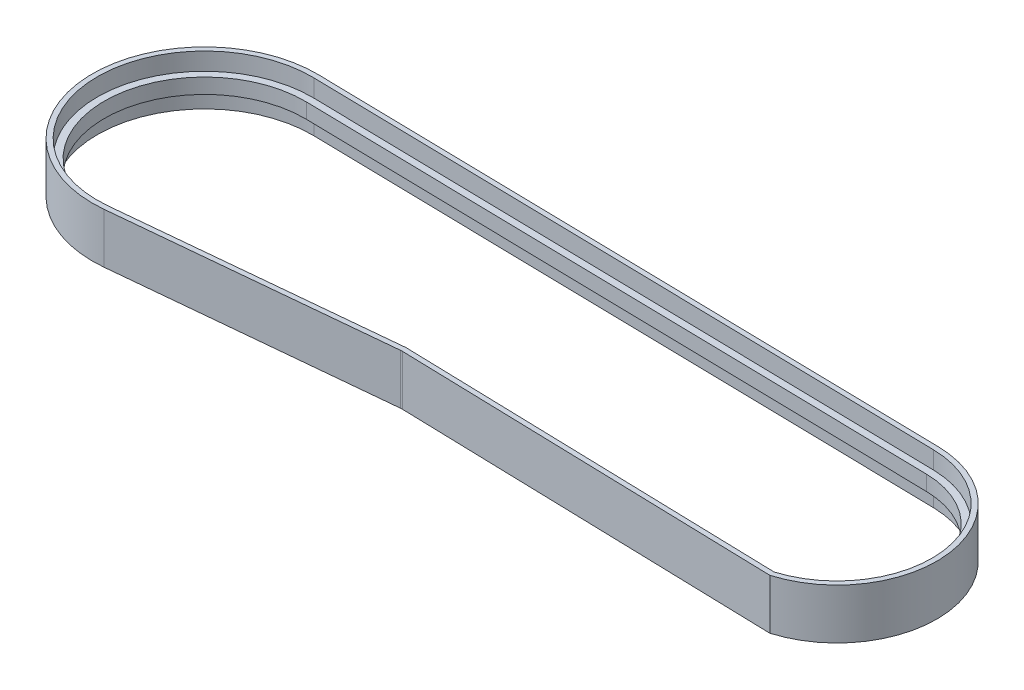
SolidWorks part; units mm, degrees
other "Markup1"
sketch "Sketch2" plane through (-23.4, 0, -23.4) normal (-0.231, -0.9167, -0.326) x (-0.972, 0.232, 0.0366)
sketch "Sketch3" plane through (-22.35, 0, -22.35) normal (-0.231, -0.9167, -0.326) x (-0.972, 0.232, 0.0366)
sketch "Sketch4" plane through (-22.35, 0, -22.35) normal (-0.231, -0.9167, -0.326) x (-0.972, 0.232, 0.0366)
sketch "Sketch5" plane through (-22.35, 0, -22.35) normal (-0.231, -0.9167, -0.326) x (-0.972, 0.232, 0.0366)
sketch "Sketch6" plane through (-22.35, 0, -22.35) normal (-0.231, -0.9167, -0.326) x (-0.972, 0.232, 0.0366)
material "BUTYL"
ref_plane "Front Plane" through (0, 0, 0) normal (0, 0, 1) x (1, 0, 0)
ref_plane "Top Plane" through (0, 0, 0) normal (0, 1, 0) x (1, 0, 0)
ref_plane "Right Plane" through (0, 0, 0) normal (1, 0, 0) x (0, 0, -1)
sketch "Sketch1" plane through (0, 0, 0) normal (0, 1, 0) x (1, 0, 0)
  line L0 (0, 0) -> (126, 0) construction
  line L1 (0.4151, 21.346) -> (126.3675, 18.8964)
  line L2 (0.4346, 22.3458) -> (126.3869, 19.8962)
  line L5 (8.122, -19.7447) -> (131.5335, -18.0718) construction
  line L6 (8.3239, -20.7421) -> (131.6879, -19.0698) construction
  line L7 (131.5335, -18.0718) -> (56.2608, -16.0228)
  line L8 (131.6879, -19.0698) -> (56.4768, -17.0225)
  line L9 (2.0539, -21.251) -> (55.9487, -16.0421)
  line L10 (2.1501, -22.2463) -> (56.0449, -17.0374)
  line L11 (0, 0) -> (56.3816, -20.5212) construction
  arc A0 (0.4151, 21.346) -> (2.0539, -21.251) centre (0, 0) ccw
  arc A1 (131.5335, -18.0718) -> (126.3675, 18.8964) centre (126, 0) ccw
  arc A2 (131.6879, -19.0698) -> (126.3869, 19.8962) centre (126, 0) ccw
  arc A3 (0.4346, 22.3458) -> (2.1501, -22.2463) centre (0, 0) ccw
  circle A4 centre (0, 0) radius 60 construction
  circle A5 centre (56.3816, -20.5212) radius 1.25 construction
  arc A6 (56.4768, -17.0225) -> (56.0449, -17.0374) centre (56.3816, -20.5212) ccw
  arc A8 (56.2608, -16.0228) -> (55.9487, -16.0421) centre (56.3816, -20.5212) ccw
  arc A9 (0.4346, 22.3458) -> (8.3239, -20.7421) centre (0, 0) ccw construction
  arc A10 (0.4151, 21.346) -> (8.122, -19.7447) centre (0, 0) ccw construction
  point P17 (45.2586, -17.6917)
  dimension "D1" = 42.7
  dimension "D3" = 37.8
  dimension "D5" = 120
  dimension "D6" = 7
  dimension "D7" = 2.5
  dimension "D9" = 1
  dimension "D2" = 126
  dimension "D8" = 20
  dimension "D4" = 1
extrude "Boss-Extrude1" add sketch "Sketch1" along normal mid plane 10
sketch "Sketch8" plane through (0, 0, 0) normal (0, 1, 0) x (1, 0, 0)
  line L15 (56.2636, -14.6224) -> (131.3381, -16.666)
  line L16 (126.3403, 17.4967) -> (0.3879, 19.9462)
  line L17 (1.9192, -19.8575) -> (55.814, -14.6486)
  line L18 (56.2636, -14.6224) -> (131.3381, -16.666)
  line L19 (126.3403, 17.4967) -> (0.3879, 19.9462)
  line L20 (1.9192, -19.8575) -> (55.814, -14.6486)
  line L32 (56.2608, -16.2229) -> (131.5607, -18.2726)
  line L33 (126.3714, 19.0964) -> (0.419, 21.5459)
  line L34 (2.0731, -21.45) -> (55.9679, -16.2412)
  line L35 (56.2608, -16.2229) -> (131.5607, -18.2726)
  line L36 (126.3714, 19.0964) -> (0.419, 21.5459)
  line L37 (2.0731, -21.45) -> (55.9679, -16.2412)
  arc A12 (56.2636, -14.6224) -> (55.814, -14.6486) centre (56.3816, -20.5212) ccw
  arc A13 (131.3381, -16.666) -> (126.3403, 17.4967) centre (126, 0) ccw
  arc A14 (0.3879, 19.9462) -> (1.9192, -19.8575) centre (0, 0) ccw
  arc A15 (56.2636, -14.6224) -> (55.814, -14.6486) centre (56.3816, -20.5212) ccw
  arc A16 (131.3381, -16.666) -> (126.3403, 17.4967) centre (126, 0) ccw
  arc A17 (0.3879, 19.9462) -> (1.9192, -19.8575) centre (0, 0) ccw
  arc A28 (56.2608, -16.2229) -> (55.9679, -16.2412) centre (56.3816, -20.5212) ccw
  arc A29 (131.5607, -18.2726) -> (126.3714, 19.0964) centre (126, 0) ccw
  arc A30 (0.419, 21.5459) -> (2.0731, -21.45) centre (0, 0) ccw
  arc A31 (56.2608, -16.2229) -> (55.9679, -16.2412) centre (56.3816, -20.5212) ccw
  arc A32 (131.5607, -18.2726) -> (126.3714, 19.0964) centre (126, 0) ccw
  arc A33 (0.419, 21.5459) -> (2.0731, -21.45) centre (0, 0) ccw
  dimension "D1" = 1.4
  dimension "D2" = 0.2
extrude "Boss-Extrude2" add sketch "Sketch8" along normal mid plane 3
